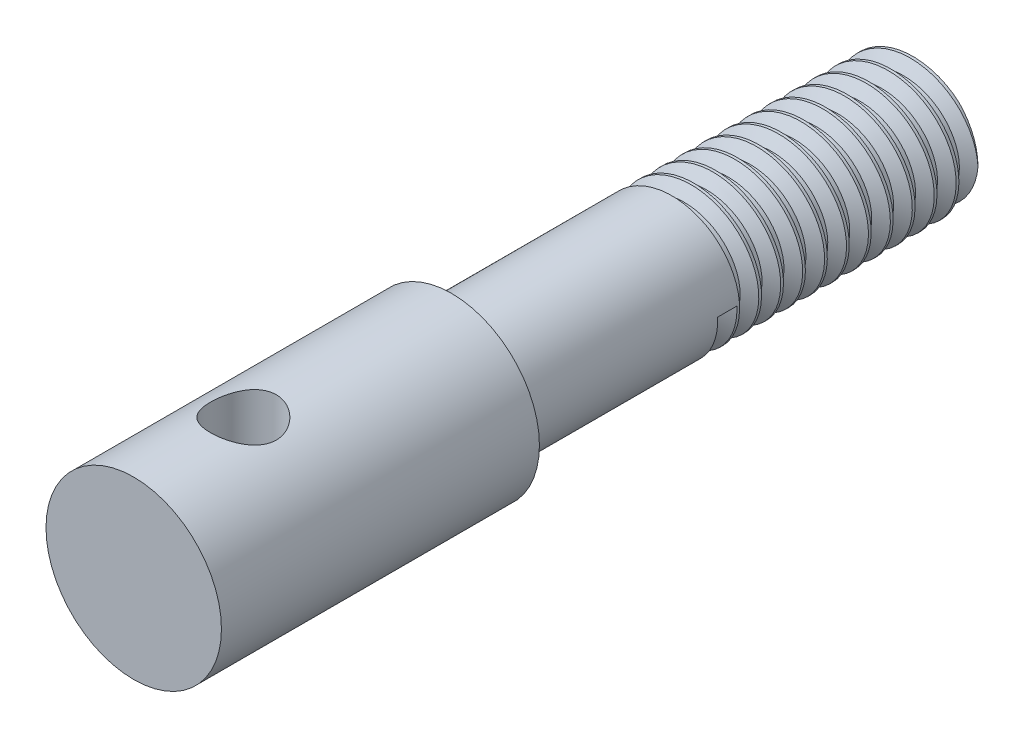
SolidWorks part; units mm, degrees
ref_plane "Alzado" through (0, 0, 0) normal (0, 0, 1) x (1, 0, 0)
ref_plane "Planta" through (0, 0, 0) normal (0, 1, 0) x (1, 0, 0)
ref_plane "Vista lateral" through (0, 0, 0) normal (1, 0, 0) x (0, 0, -1)
sketch "Croquis1" plane through (0, 0, 0) normal (0, 0, 1) x (1, 0, 0)
  circle A0 centre (0, 0) radius 4
  dimension "D1" = 8
extrude "Saliente-Extruir1" add sketch "Croquis1" along normal blind 39.5
ref_plane "Plano1" through (0, 4, 0) normal (0, 1, 0) x (1, 0, 0)
sketch "Croquis2" plane through (0, 4, 0) normal (0, 1, 0) x (1, 0, 0)
  line L0 (-4, -39.5) -> (4, -39.5) construction
  line L1 (-4, 0) -> (-4, -39.5) construction
  circle A0 centre (0, -34.5) radius 1.5
  dimension "D1" = 3
  dimension "D2" = 5
  dimension "D3" = 4
extrude "Cortar-Extruir1" cut sketch "Croquis2" against normal through all
sketch "Croquis3" plane through (0, 0, 0) normal (0, 0, -1) x (-1, 0, 0)
  circle A0 centre (0, 0) radius 3
  circle A2 centre (0, 0) radius 4
  dimension "D1" = 6
  dimension "D2" = 8
extrude "Cortar-Extruir2" cut sketch "Croquis3" against normal blind 25
thread "Rosca1" pitch 1 method cut profile "Perfil de rosca1" start angle 0, offset 0, length 15, pitch 1, diameter 6
ref_plane "Plano2" through (3, 0, 0) normal (0, -1, 0) x (1, 0, 0)
sketch "Perfil de rosca1" plane through (3, 0, 0) normal (0, -1, 0) x (1, 0, 0)
  line L0 (0, 0) -> (0, 1) construction
  line L11 (0, 0) -> (0, 0.875)
  line L12 (0, 0.875) -> (-0.5413, 0.5625)
  line L13 (-0.5413, 0.5625) -> (-0.5413, 0.3125)
  line L15 (-0.5413, 0.3125) -> (0, 0)
  line L17 (-0.5413, 0.4375) -> (0, 0.4375) construction
  point P2 (0, 0)
  dimension "Pitch" = 1
  dimension "Profile_Angle" = 60
  dimension "Profile_Land" = 0.25
  dimension "Profile_Height" = 0.5413
ref_plane "Plano3" through (0, 4, 0) normal (0, 1, 0) x (1, 0, 0)
sketch "Croquis8" plane through (0, 4, 0) normal (0, 1, 0) x (1, 0, 0)
  line L0 (-10, 0) -> (10, 0)
  line L1 (-10, 0) -> (-10, -4)
  line L2 (-10, -4) -> (10, -4)
  line L3 (10, -4) -> (10, 0)
  line L4 (3, 0) -> (-3, 0) construction
  line L5 (0, 0) -> (0, 3.2967) construction
  dimension "D1" = 4
  dimension "D2" = 20
extrude "Cortar-Extruir3" cut sketch "Croquis8" against normal through all
